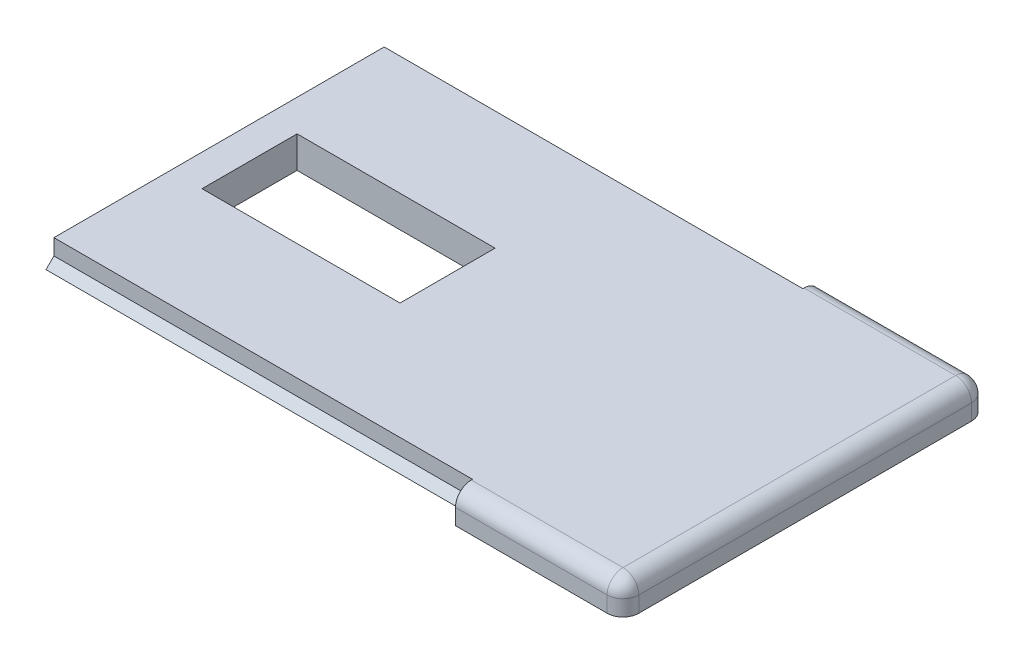
SolidWorks part; units mm, degrees
ref_plane "前视基准面" through (0, 0, 0) normal (0, 0, 1) x (1, 0, 0)
ref_plane "上视基准面" through (0, 0, 0) normal (0, 1, 0) x (1, 0, 0)
ref_plane "右视基准面" through (0, 0, 0) normal (1, 0, 0) x (0, 0, -1)
sketch "草图1" plane through (0, 0, 0) normal (0, 1, 0) x (1, 0, 0)
  line L0 (-35, -21) -> (35, -21)
  line L1 (-35, -21) -> (-35, 21)
  line L2 (-35, 21) -> (35, 21)
  line L3 (35, -21) -> (35, 21)
  line L4 (-35, -21) -> (35, 21) construction
  line L5 (-35, 21) -> (35, -21) construction
  line L10 (35, -21) -> (31, -21)
  line L11 (35, -21) -> (35, -18)
  line L14 (35, 21) -> (31, 21)
  line L15 (35, 21) -> (35, 18)
  line L18 (-35, -21) -> (-23, -21)
  line L19 (-35, -21) -> (-35, -18)
  line L22 (-37, -23) -> (37, -23)
  line L23 (-37, -23) -> (-37, 23)
  line L24 (-37, 23) -> (37, 23)
  line L25 (37, -23) -> (37, 23)
  line L26 (-37, -23) -> (37, 23) construction
  line L27 (-37, 23) -> (37, -23) construction
  line L28 (-34.85, -20.85) -> (-34.85, 20.85)
  line L29 (37, 23) -> (17, 23)
  line L30 (37, 23) -> (37, -23)
  line L31 (37, -23) -> (17, -23)
  line L32 (17, 23) -> (17, -23)
  line L33 (-35, -21) -> (17, -21)
  line L34 (-35, -21) -> (-35, 21)
  line L35 (-35, 21) -> (17, 21)
  line L36 (17, -21) -> (17, 21)
  line L37 (-34.85, 20.85) -> (16.85, 20.85)
  line L39 (-34.85, -20.85) -> (16.85, -20.85)
  line L40 (16.85, 20.85) -> (17, 20.85)
  line L41 (16.85, -20.85) -> (17, -20.85)
  line L43 (16.85, -20.85) -> (16.85, 20.85) construction
  point P0 (0, 0)
  point P21 (0, 0)
  dimension "D1" = 46
  dimension "D2" = 74
  dimension "D3" = 42
  dimension "D4" = 70
  dimension "D5" = 46
  dimension "D6" = 20
  dimension "D7" = 0.15
extrude "凸台-拉伸2" add sketch "草图1" along normal blind 4 contours L39 L41 L36 L40 L37 L28 | L2 L32 L36 L0 L3 | L24 L32 L2 L3 L0 L22 L25 region at (26, 0, 0) region at (24, 0, 21.5016) region at (-8.925, 0, 0)
sketch "草图3" plane through (17, 0, 0) normal (-1, 0, 0) x (0, 0, 1)
  line L0 (20.85, 2) -> (21.85, 1)
  line L1 (20.85, 4) -> (20.85, 0) construction
  line L2 (21.85, 1) -> (20.85, 0)
  line L3 (20.85, 4) -> (20.85, 0) construction
  line L4 (20.85, 0) -> (20.85, 2)
  line L5 (20.85, 0) -> (23, 0) construction
  dimension "D1" = 45
  dimension "D2" = 45
  dimension "D3" = 1
sketch "草图4" plane through (17, 0, 0) normal (-1, 0, 0) x (0, 0, 1)
  line L0 (-20.85, 2) -> (-21.85, 1)
  line L1 (-20.85, 4) -> (-20.85, 0) construction
  line L2 (-21.85, 1) -> (-20.85, 0)
  line L3 (-20.85, 4) -> (-20.85, 0) construction
  line L4 (-20.85, 0) -> (-20.85, 2)
  line L5 (-23, 0) -> (-20.85, 0) construction
  dimension "D1" = 45
  dimension "D2" = 45
  dimension "D3" = 1
extrude "凸台-拉伸3" add sketch "草图4" along normal up to surface (51.85 mm away) up to face at (-34.85, 2, 0)
extrude "凸台-拉伸4" add sketch "草图3" along normal up to surface (51.85 mm away) up to face at (-34.85, 1.8333, -7.1167)
sketch "草图6" plane through (0, 4, 0) normal (0, 1, 0) x (1, 0, 0)
  line L1 (-34.85, 20.85) -> (-31.85, 20.85)
  line L2 (-34.85, 20.85) -> (-34.85, 5.85)
  line L3 (-34.85, 5.85) -> (-31.85, 5.85)
  line L4 (-31.85, 20.85) -> (-31.85, 5.85)
  line L5 (-34.85, 20.85) -> (-6.85, 20.85)
  line L6 (-34.85, 20.85) -> (-34.85, -6.15)
  line L7 (-34.85, -6.15) -> (-6.85, -6.15)
  line L8 (-34.85, -20.85) -> (17, -20.85)
  line L9 (17, -20.85) -> (17, -23)
  line L10 (17, -23) -> (37, -23)
  line L11 (37, -23) -> (37, 23)
  line L12 (37, 23) -> (17, 23)
  line L13 (17, 23) -> (17, 20.85)
  line L14 (17, 20.85) -> (-34.85, 20.85)
  line L15 (-34.85, 20.85) -> (-34.85, -20.85)
  line L16 (-34.85, -20.85) -> (17, -20.85)
  line L17 (17, -20.85) -> (17, -23)
  line L18 (17, -23) -> (37, -23)
  line L19 (37, -23) -> (37, 23)
  line L20 (37, 23) -> (17, 23)
  line L21 (17, 23) -> (17, 20.85)
  line L22 (17, 20.85) -> (-34.85, 20.85)
  line L23 (-34.85, 20.85) -> (-34.85, -20.85)
  line L24 (-6.85, 20.85) -> (-6.85, -6.15)
  line L25 (-31.85, 5.85) -> (-6.85, 5.85)
  line L26 (-31.85, 5.85) -> (-31.85, -6.15)
  line L27 (-31.85, -6.15) -> (-6.85, -6.15)
  line L28 (-6.85, 5.85) -> (-6.85, -6.15)
  point P2 (-34.85, 0)
  dimension "D2" = 15
  dimension "D3" = 3
  dimension "D4" = 27
  dimension "D5" = 28
  dimension "D1" = 0
extrude "切除-拉伸1" cut sketch "草图6" against normal up to surface (4 mm away) contours L25 L26 L7 L24 region at (-19.35, 4, 0.15) up to face at (9.0375, 0, 0)
sketch "草图7" plane through (37, 0, 0) normal (1, 0, 0) x (0, 0, -1)
  line L8 (-23, 0) -> (23, 0)
  line L9 (23, 0) -> (23, 4)
  line L10 (23, 4) -> (-23, 4)
  line L11 (-23, 4) -> (-23, 0)
  line L12 (-23, 0) -> (23, 0)
  line L13 (23, 0) -> (23, 4)
  line L14 (23, 4) -> (-23, 4)
  line L15 (-23, 4) -> (-23, 0)
  dimension "D1" = 0
extrude "凸台-拉伸5" add sketch "草图7" along normal blind 1.15
sketch "草图10" plane through (0, 4, 0) normal (0, 1, 0) x (1, 0, 0)
  line L1 (38.15, 23) -> (35.15, 23)
  line L2 (38.15, 23) -> (38.15, -23)
  line L3 (38.15, -23) -> (35.15, -23)
  line L4 (35.15, 23) -> (35.15, -23)
  line L5 (17, -23) -> (38.15, -23) construction
  line L6 (38.15, 0) -> (35.15, 0)
  point P10 (36.65, 0)
  dimension "D1" = 46
  dimension "D2" = 3
ref_plane "基准面4" through (0, 0, 0) normal (0, 0, 1) x (1, 0, 0)
sketch "草图11" plane through (0, 0, 0) normal (0, 0, 1) x (1, 0, 0)
  line L0 (35.9, 4) -> (36.65, 3.25)
  line L1 (38.15, 4) -> (35.15, 4) construction
  line L2 (36.65, 3.25) -> (37.4, 4)
  line L3 (36.65, 3.25) -> (36.65, 4)
  line L4 (37.4, 4) -> (35.9, 4)
  line L5 (35.9, 4) -> (36.65, 4.75)
  line L6 (36.65, 4.75) -> (37.4, 4)
  dimension "D1" = 45
  dimension "D2" = 45
  dimension "D3" = 0.75
sketch "草图12" plane through (0, 0, 0) normal (0, 0, 1) x (1, 0, 0)
  line L4 (36.65, -0.75) -> (36.65, 0)
  line L5 (38.15, 0) -> (35.15, 0)
  line L6 (17, 0) -> (38.15, 0) construction
  line L7 (37.4, 0) -> (36.65, -0.75)
  line L8 (36.65, -0.75) -> (35.9, 0)
  point P0 (36.65, 0)
  dimension "D1" = 45
  dimension "D2" = 45
  dimension "D3" = 0.75
  dimension "D4" = 3
extrude "凸台-拉伸6" add sketch "草图12" along normal mid plane 10 contours L7 L5 L4 | L8 L4 L5 region at (36.4, -0.25, 0) region at (36.9, -0.25, 0)
sketch "草图13" plane through (0, 4, 0) normal (0, 1, 0) x (1, 0, 0)
  line L8 (-34.85, -20.85) -> (17, -20.85)
  line L9 (17, -20.85) -> (17, -23)
  line L10 (17, -23) -> (38.15, -23)
  line L11 (38.15, -23) -> (38.15, 23)
  line L12 (38.15, 23) -> (17, 23)
  line L13 (17, 23) -> (17, 20.85)
  line L14 (17, 20.85) -> (-34.85, 20.85)
  line L15 (-34.85, 20.85) -> (-34.85, -20.85)
  line L16 (-34.85, -20.85) -> (17, -20.85)
  line L17 (17, -20.85) -> (17, -23)
  line L18 (17, -23) -> (38.15, -23)
  line L19 (38.15, -23) -> (38.15, 23)
  line L20 (38.15, 23) -> (17, 23)
  line L21 (17, 23) -> (17, 20.85)
  line L22 (17, 20.85) -> (-34.85, 20.85)
  line L23 (-34.85, 20.85) -> (-34.85, -20.85)
  dimension "D1" = 0
sketch "草图14" plane through (-34.85, 0, 0) normal (-1, 0, 0) x (0, 0, 1)
  line L8 (-20.85, 0) -> (20.85, 0)
  line L9 (20.85, 0) -> (21.85, 1)
  line L10 (21.85, 1) -> (20.85, 2)
  line L11 (20.85, 2) -> (20.85, 4)
  line L12 (20.85, 4) -> (-20.85, 4)
  line L13 (-20.85, 4) -> (-20.85, 2)
  line L14 (-20.85, 2) -> (-21.85, 1)
  line L15 (-21.85, 1) -> (-20.85, 0)
  line L16 (-20.85, 0) -> (20.85, 0)
  line L17 (20.85, 0) -> (21.85, 1)
  line L18 (21.85, 1) -> (20.85, 2)
  line L19 (20.85, 2) -> (20.85, 4)
  line L20 (20.85, 4) -> (-20.85, 4)
  line L21 (-20.85, 4) -> (-20.85, 2)
  line L22 (-20.85, 2) -> (-21.85, 1)
  line L23 (-21.85, 1) -> (-20.85, 0)
  dimension "D1" = 0
extrude "凸台-拉伸7" add sketch "草图14" along normal blind 1 contours L16 L17 L18 L19 L20 L21 L22 L23
fillet "圆角3" radius 2 5 edges at (27.575, 4, -23) (38.15, 4, 0) (27.575, 4, 23) (38.15, 2, 23) (38.15, 2, -23)
